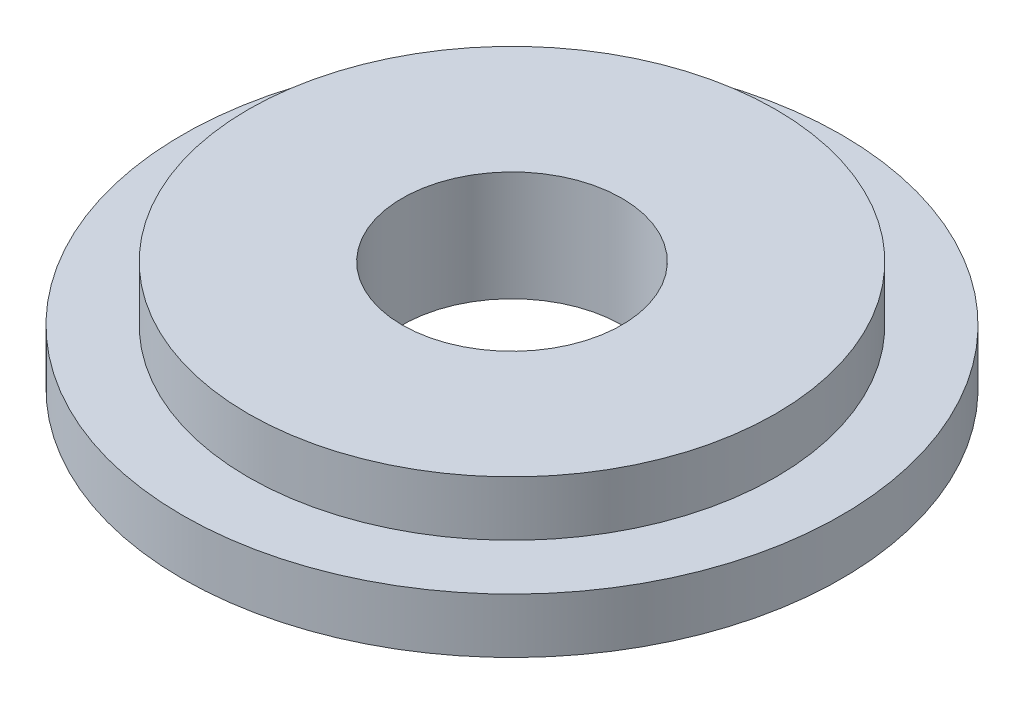
SolidWorks part; units mm, degrees
ref_plane "Front Plane" through (0, 0, 0) normal (0, 0, 1) x (1, 0, 0)
ref_plane "Top Plane" through (0, 0, 0) normal (0, 1, 0) x (1, 0, 0)
ref_plane "Right Plane" through (0, 0, 0) normal (1, 0, 0) x (0, 0, -1)
sketch "Croquis1" plane through (0, 0, 0) normal (0, 1, 0) x (1, 0, 0)
  circle A0 centre (0, 0) radius 24
  circle A1 centre (0, 0) radius 30
  circle A2 centre (0, 0) radius 10
  dimension "D1" = 48
  dimension "D2" = 60
  dimension "D3" = 20
extrude "Saliente-Extruir1" add sketch "Croquis1" along normal blind 5 contours A0 A2 region at (-23.3212, 0, 0)
extrude "Saliente-Extruir2" add sketch "Croquis1<3>" against normal blind 5 contours A1 A0 | A0 A2 region at (-23.3212, 0, 0) region at (-29.1515, 0, 0)
sketch "Croquis1<3>" plane through (0, 0, 0) normal (0, 1, 0) x (1, 0, 0) same geometry as "Croquis1"
equation "\"ID\"=48"
equation "\"D1@Croquis1\"=\"ID\""
equation "\"OD\"=60"
equation "\"D2@Croquis1\"=\"OD\""
equation "\"Dmandril\"=20"
equation "\"D3@Croquis1\"=\"Dmandril\""
